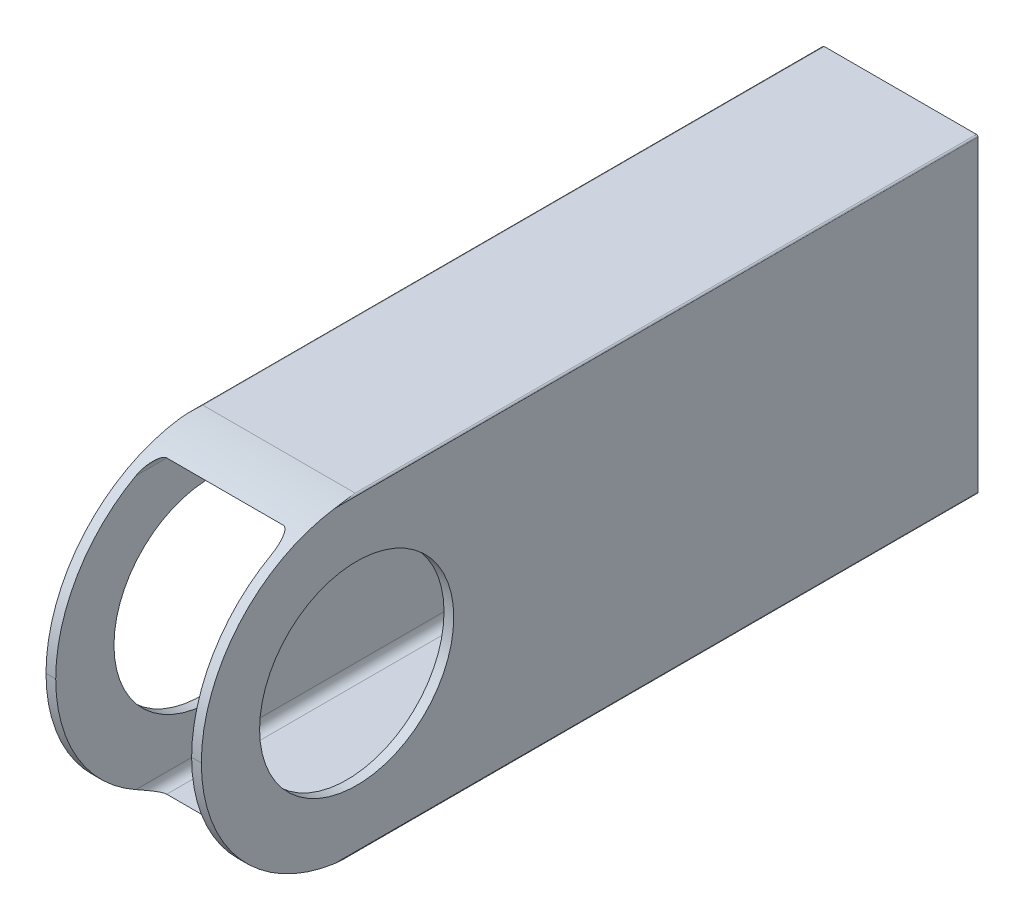
SolidWorks part; units mm, degrees
ref_plane "Front Plane" through (0, 0, 0) normal (0, 0, 1) x (1, 0, 0)
ref_plane "Top Plane" through (0, 0, 0) normal (0, 1, 0) x (1, 0, 0)
ref_plane "Right Plane" through (0, 0, 0) normal (1, 0, 0) x (0, 0, -1)
ref_plane "Plane1" through (0, 0, 0) normal (0, 0, -1) x (-1, 0, 0)
sketch "Sketch1" plane through (0, 0, 0) normal (0, 0, -1) x (-1, 0, 0)
  line L0 (-11.1125, -22.225) -> (-11.1125, 22.225)
  line L1 (-9.525, 23.8125) -> (9.525, 23.8125)
  line L2 (11.1125, 22.225) -> (11.1125, -22.225)
  line L3 (9.525, -23.8125) -> (-9.525, -23.8125)
  line L4 (-12.7, 25.146) -> (-12.7, -25.146)
  line L5 (-12.446, -25.4) -> (12.446, -25.4)
  line L6 (12.7, -25.146) -> (12.7, 25.146)
  line L7 (12.446, 25.4) -> (-12.446, 25.4)
  arc A0 (-11.1125, 22.225) -> (-9.525, 23.8125) centre (-9.525, 22.225) cw
  arc A1 (9.525, 23.8125) -> (11.1125, 22.225) centre (9.525, 22.225) cw
  arc A2 (11.1125, -22.225) -> (9.525, -23.8125) centre (9.525, -22.225) cw
  arc A3 (-9.525, -23.8125) -> (-11.1125, -22.225) centre (-9.525, -22.225) cw
  arc A4 (-12.7, -25.146) -> (-12.446, -25.4) centre (-12.446, -25.146) ccw
  arc A5 (12.446, -25.4) -> (12.7, -25.146) centre (12.446, -25.146) ccw
  arc A6 (12.7, 25.146) -> (12.446, 25.4) centre (12.446, 25.146) ccw
  arc A7 (-12.446, 25.4) -> (-12.7, 25.146) centre (-12.446, 25.146) ccw
extrude "Boss-Extrude1" add sketch "Sketch1" against normal blind 127
sketch "Sketch2" plane through (12.7, 0, 0) normal (1, 0, 0) x (0, 0, -1)
  line L0 (-127, 0) -> (-101.6, 0) construction
  line L1 (-127, 25.146) -> (-127, -25.146) construction
  circle A0 centre (-101.6, 0) radius 15.875
  dimension "D1" = 31.75
  dimension "D2" = 25.4
extrude "Cut-Extrude1" cut sketch "Sketch2" against normal blind 25.4
fillet "Fillet2" radius 25.4 2 edges at (0, -25.4, 127) (0, 25.4, 127) tangent propagation no
